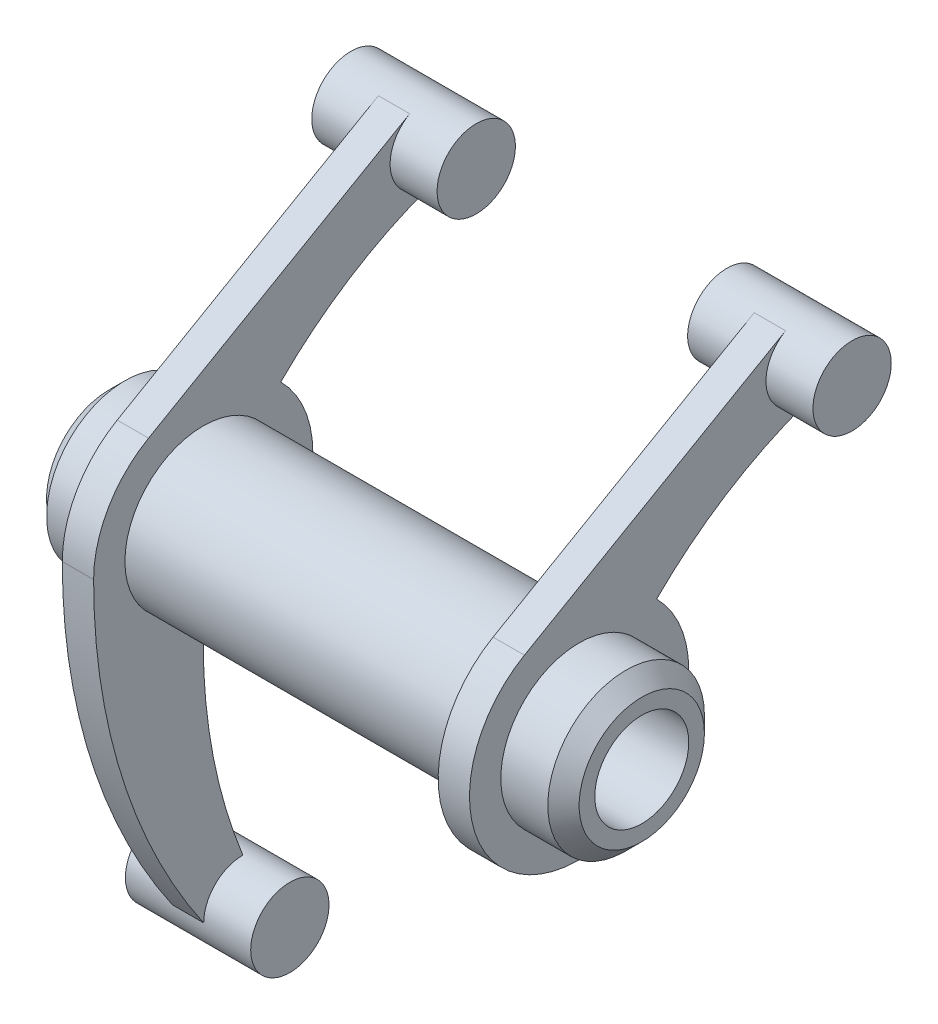
SolidWorks part; units mm, degrees
material "AISI 8620 Steel, carburized"
ref_plane "Front Plane" through (0, 0, 0) normal (1, 0, 0) x (0, 1, 0)
ref_plane "Top Plane" through (0, 0, 0) normal (0, 0, 1) x (0, 1, 0)
ref_plane "Right Plane" through (0, 0, 0) normal (0, 1, 0) x (-1, 0, 0)
sketch "Sketch1" plane through (0, 0, 0) normal (1, 0, 0) x (0, 1, 0)
  line L0 (6.0665, 3.4925) -> (15.6666, -13.1827)
  line L1 (9.4815, -14.43) -> (19.5827, -14.43) construction
  line L2 (0, 0) -> (4.9497, -4.9497) construction
  line L3 (-9.5267, 0) -> (15.6666, 0) construction
  arc A0 (6.0665, 3.4925) -> (4.9497, -4.9497) centre (0, 0) ccw
  circle A1 centre (0, 0) radius 5
  circle A2 centre (13.5, -14.43) radius 2.5
  arc A3 (4.9497, -4.9497) -> (11, -14.43) centre (-13.5011, -23.3957) cw
  circle A4 centre (0, 0) radius 4
  circle A5 centre (0, 0) radius 3
  dimension "D1" = 14
  dimension "D2" = 10
  dimension "D3" = 5
  dimension "D4" = 26.09
  dimension "D7" = 8
  dimension "D8" = 6
  dimension "D9" = 45
  dimension "D5" = 14.43
  dimension "D6" = 13.5
extrude "Boss-Extrude1" add sketch "Sketch1" along normal mid plane 8 contours A2 region at (0, 13.5, -14.43)
extrude "Boss-Extrude2" add sketch "Sketch1<3>" along normal mid plane 2 contours A0 A3 A2 L0 A1 region at (0, 4.1091, -2.9421)
sketch "Sketch1<3>" plane through (0, 0, 0) normal (1, 0, 0) x (0, 1, 0) same geometry as "Sketch1"
extrude "Boss-Extrude3" add sketch "Sketch1<4>" along normal blind 6 and the other way blind 28 from surface contours A1 | A5 starting at face at (-1, 0, -5)
sketch "Sketch1<4>" plane through (0, 0, 0) normal (1, 0, 0) x (0, 1, 0) same geometry as "Sketch1"
ref_plane "Plane1" through (-23, 0, 0) normal (-1, 0, 0) x (0, -1, 0)
sketch "Sketch2" plane through (-23, 0, 0) normal (-1, 0, 0) x (0, -1, 0)
  line L0 (-6.0665, 3.4925) -> (-15.6666, -13.1827) construction
  line L1 (-6.0665, 3.4925) -> (-15.6666, -13.1827)
  line L2 (-9.0524, 0) -> (7, 0) construction
  line L3 (22.5, -0.03) -> (22.5, -7.2634) construction
  line L4 (20, -2.53) -> (27.2188, -2.53) construction
  circle A0 centre (-13.5, -14.43) radius 2.5 construction
  circle A1 centre (-13.5, -14.43) radius 2.5
  circle A2 centre (0, 0) radius 5 construction
  arc A3 (-4.9497, -4.9497) -> (-6.0665, 3.4925) centre (0, 0) ccw construction
  circle A4 centre (0, 0) radius 5
  arc A5 (-4.9497, -4.9497) -> (-6.0665, 3.4925) centre (0, 0) ccw
  arc A6 (-4.9497, -4.9497) -> (-11, -14.43) centre (13.5011, -23.3957) ccw construction
  arc A7 (-4.9497, -4.9497) -> (-11, -14.43) centre (13.5011, -23.3957) ccw
  circle A8 centre (22.5, -2.53) radius 2.5
  arc A9 (22.5, -0.03) -> (-0.0001, 7) centre (0.0004, -32.52) ccw
  arc A10 (7, 0) -> (20, -2.53) centre (7.0008, -34.66) cw
  dimension "D1" = 5
  dimension "D4" = 39.52
  dimension "D5" = 34.66
  dimension "D2" = 22.5
  dimension "D3" = 11.9
extrude "Boss-Extrude6" add sketch "Sketch2" along normal blind 2 contours A7 A5 L1 A1 A4 | A5 A10 A8 A9 region at (-23, 4.1091, -2.9421) region at (-23, -12.5044, 2.2126)
extrude "Boss-Extrude7" add sketch "Sketch2<5>" along normal blind 5 and the other way blind 3 contours A8 | A1 region at (-23, 13.5, -14.43) region at (-23, -22.5, -2.53)
sketch "Sketch2<5>" plane through (-23, 0, 0) normal (-1, 0, 0) x (0, -1, 0) same geometry as "Sketch2"
chamfer "Chamfer1" distance 1 angle 45 2 edges at (-29, 0, -5) (5, 0, -5)
ref_plane "Plane2" through (-12, 0, 0) normal (-1, 0, 0) x (0, -1, 0)
ref_plane "Plane3" through (-24, 0, 0) normal (-1, 0, 0) x (0, -1, 0)
